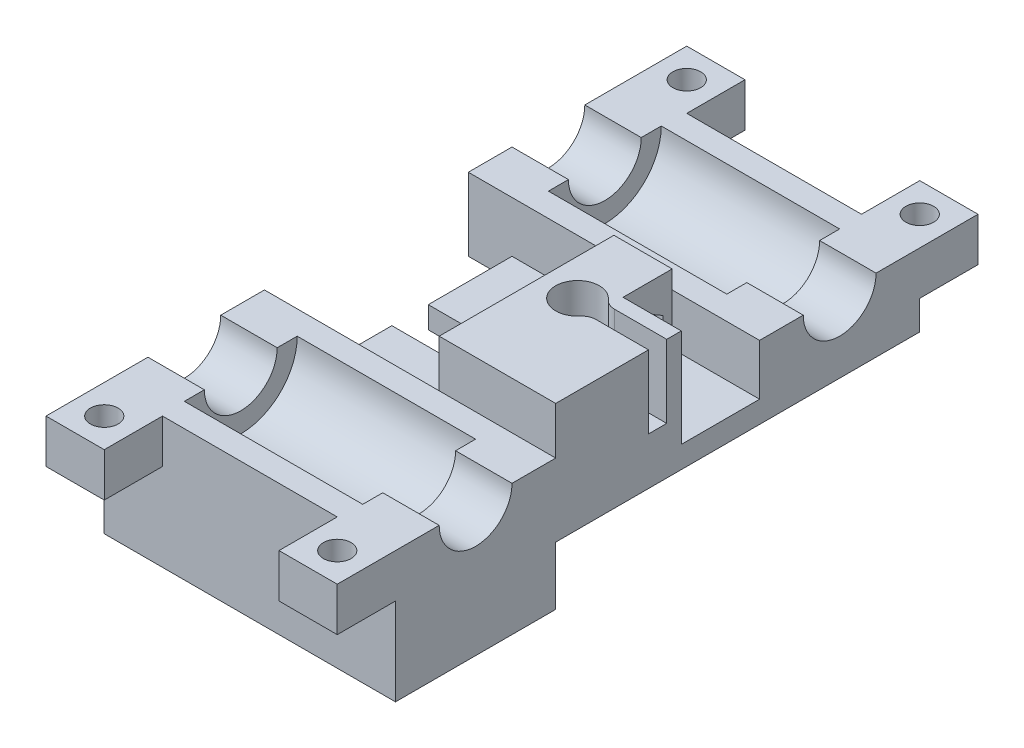
SolidWorks part; units mm, degrees
ref_plane "Front Plane" through (0, 0, 0) normal (0, 0, 1) x (1, 0, 0)
ref_plane "Top Plane" through (0, 0, 0) normal (0, 1, 0) x (1, 0, 0)
ref_plane "Right Plane" through (0, 0, 0) normal (1, 0, 0) x (0, 0, -1)
sketch "Sketch1" plane through (0, 0, 0) normal (0, 1, 0) x (1, 0, 0)
  line L1 (-20, 11) -> (20, 11)
  line L2 (-20, 11) -> (-20, -11)
  line L3 (-20, -11) -> (20, -11)
  line L4 (20, 11) -> (20, -11)
  line L5 (-20, 11) -> (20, -11) construction
  line L6 (-20, -11) -> (20, 11) construction
  point P0 (0, 0)
  dimension "D1" = 40
  dimension "D2" = 22
extrude "Boss-Extrude1" add sketch "Sketch1" along normal blind 11
sketch "Sketch2" plane through (0, 0, 0) normal (0, 1, 0) x (1, 0, 0)
  line L4 (20, -11) -> (20, 11)
  line L5 (-20, -11) -> (20, -11)
  line L6 (-20, 11) -> (-20, -11)
  line L7 (20, 11) -> (-20, 11)
  line L8 (20, -11) -> (20, 11)
  line L9 (-20, -11) -> (20, -11)
  line L10 (-20, 11) -> (-20, -11)
  line L11 (20, 11) -> (-20, 11)
  circle A0 centre (0, 0) radius 4.25
  dimension "D2" = 8.5
  dimension "D1" = 0
extrude "Boss-Extrude2" add sketch "Sketch2" against normal blind 7
sketch "Sketch3" plane through (0, 11, 0) normal (0, 1, 0) x (1, 0, 0)
  line L1 (12.25, -7.75) -> (-12.25, -7.75)
  line L2 (12.25, -7.75) -> (12.25, 7.75)
  line L3 (12.25, 7.75) -> (-12.25, 7.75)
  line L4 (-12.25, -7.75) -> (-12.25, 7.75)
  line L5 (12.25, -7.75) -> (-12.25, 7.75) construction
  line L6 (12.25, 7.75) -> (-12.25, -7.75) construction
  point P0 (0, 0)
  dimension "D1" = 15.5
  dimension "D2" = 24.5
extrude "Cut-Extrude1" cut sketch "Sketch3" against normal blind 7.75
fillet "Fillet1" radius 7.75 2 edges at (0, 3.25, 7.75) (0, 3.25, -7.75)
sketch "Sketch4" plane through (-12.25, 0, 0) normal (1, 0, 0) x (0, 0, -1)
  line L0 (7.75, 11) -> (-7.75, 11) construction
  circle A0 centre (0, 11) radius 5
  dimension "D1" = 10
extrude "Cut-Extrude2" cut sketch "Sketch4" against normal through all both and the other way through all
sketch "Sketch5" plane through (0, 11, 0) normal (0, 1, 0) x (1, 0, 0)
  line L1 (20, -11) -> (12, -11)
  line L2 (20, -11) -> (20, -19)
  line L3 (20, -19) -> (12, -19)
  line L4 (12, -11) -> (12, -19)
  circle A0 centre (16, -15) radius 1.9058
  dimension "D1" = 8
  dimension "D2" = 8
  dimension "D3" = 4
  dimension "D4" = 4
extrude "Boss-Extrude3" add sketch "Sketch5" against normal blind 6
sketch "Sketch6" plane through (0, 5, 0) normal (0, -1, 0) x (1, 0, 0)
  line L4 (20, 11) -> (20, 19)
  line L5 (20, 19) -> (12, 19)
  line L6 (12, 19) -> (12, 11)
  line L7 (12, 11) -> (20, 11)
  line L8 (20, 11) -> (20, 19)
  line L9 (20, 19) -> (12, 19)
  line L10 (12, 19) -> (12, 11)
  line L11 (12, 11) -> (20, 11)
  circle A0 centre (16, 15) radius 1.9058 construction
  circle A1 centre (16, 15) radius 1.9058
  circle A2 centre (16, 15) radius 3
  circle M6 centre (16, 15) radius 1.9058
  dimension "D2" = 6
  dimension "D1" = 0
extrude "Cut-Extrude3" cut sketch "Sketch6" against normal blind 3 contours A2 M6 region at (13.0849, 5, 15)
mirror "Mirror8" about plane through (0, 0, 0) normal (1, 0, 0) of "Cut-Extrude3", "Boss-Extrude3"
mirror "Mirror9" [suppressed] about plane through (0, 0, 0) normal (0, 0, 1)
chamfer "Chamfer2" [suppressed] distance 4 angle 45
ref_plane "Plane1" through (0, 0, -25) normal (0, 0, 1) x (1, 0, 0)
sketch "Sketch7" plane through (0, 0, -11) normal (0, 0, -1) x (-1, 0, 0)
  line L0 (-20, 11) -> (-20, -7) construction
  line L1 (-20, 1) -> (-4, 1)
  line L2 (-20, 1) -> (-20, 17.5)
  line L3 (-20, 17.5) -> (-4, 17.5)
  line L4 (-4, 1) -> (-4, 17.5)
  line L5 (-20, 11) -> (20, 11) construction
  dimension "D1" = 16
  dimension "D2" = 16.5
  dimension "D3" = 6.5
extrude "Boss-Extrude5" add sketch "Sketch7" along normal blind 28
mirror "Mirror14" about plane through (0, 0, -25) normal (0, 0, 1) of "Mirror8", "Cut-Extrude3", "Boss-Extrude3", "Cut-Extrude2", "Fillet1", "Cut-Extrude1", "Boss-Extrude2", "Boss-Extrude1"
sketch "Sketch9" plane through (4, 0, 0) normal (-1, 0, 0) x (0, 0, 1)
  line L0 (-39, 1) -> (-39, 11) construction
  line L1 (-11, 1) -> (-39, 1)
  line L2 (-11, 1) -> (-11, 4)
  line L3 (-11, 4) -> (-39, 4)
  line L4 (-39, 1) -> (-39, 4)
  dimension "D1" = 3
extrude "Boss-Extrude6" add sketch "Sketch9" along normal blind 18
sketch "Sketch10" plane through (0, 17.5, 0) normal (0, 1, 0) x (1, 0, 0)
  line L0 (-13.475, 25) -> (13.475, 25) construction
  line L1 (20, 39) -> (20, 11) construction
  line L3 (9, 23.75) -> (20, 23.75)
  line L4 (9, 23.75) -> (9, 26.25)
  line L5 (9, 26.25) -> (20, 26.25)
  line L6 (20, 23.75) -> (20, 26.25)
  circle A0 centre (9, 25) radius 3
  line M4 (20, 11) -> (20, 39)
  dimension "D3" = 6
  dimension "D1" = 0
  dimension "D2" = 11
  dimension "D4" = 2.5
  dimension "D5" = 1.25
extrude "Cut-Extrude4" cut sketch "Sketch10" against normal blind 10 contours L3 A0 L5 L4 | L5 A0 L3 L4 | A0 L3 L5 M4 region at (10.4565, 17.5, -25) region at (8.4952, 17.5, -25) region at (15.955, 17.5, -25)
sketch "Sketch11" plane through (0, 7.5, 0) normal (0, 1, 0) x (1, 0, 0)
  arc A0 (11.7272, 26.25) -> (11.7272, 23.75) centre (9, 25) ccw construction
  arc A1 (11.7272, 26.25) -> (11.7272, 23.75) centre (9, 25) ccw
  circle A2 centre (9, 25) radius 1.75
  dimension "D1" = 3.5
extrude "Cut-Extrude5" cut sketch "Sketch11" against normal through all both and the other way through all contours A2 region at (9, 7.5, -25)
sketch "Sketch12" plane through (4, 0, 0) normal (-1, 0, 0) x (0, 0, 1)
  line L1 (-39, 4) -> (-39, 11) construction
  circle A0 centre (-31, 11) radius 1.75
  dimension "D3" = 3.5
  dimension "D1" = 0
  dimension "D2" = 8
extrude "Cut-Extrude6" cut sketch "Sketch12" against normal through all both and the other way through all
sketch "Sketch15" plane through (20, 0, 0) normal (1, 0, 0) x (0, 0, -1)
  line L1 (32.6923, 13.6869) -> (29.5192, 13.809)
  line L2 (29.5192, 13.809) -> (27.8269, 11.1221)
  line L3 (27.8269, 11.1221) -> (29.3077, 8.3131)
  line L4 (29.3077, 8.3131) -> (32.4808, 8.191)
  line L5 (32.4808, 8.191) -> (34.1731, 10.8779)
  line L6 (34.1731, 10.8779) -> (32.6923, 13.6869)
  circle A0 centre (31, 11) radius 1.75 construction
  circle A1 centre (31, 11) radius 1.75
  circle A2 centre (31, 11) radius 2.75 construction
  dimension "D1" = 5.5
extrude "Cut-Extrude9" [suppressed] cut sketch "Sketch15" against normal blind 12 contours L1 L2 L3 L4 L5 L6
sketch "Sketch16" [suppressed] plane through (20, 0, 0) normal (1, 0, 0) x (0, 0, -1)
  line L1 (27, 11) -> (39, 11)
  line L2 (27, 11) -> (27, 17.5)
  line L3 (27, 17.5) -> (39, 17.5)
  line L4 (39, 11) -> (39, 17.5)
  circle A0 centre (31, 11) radius 1.75 construction
  circle A1 centre (31, 11) radius 1.75
  circle A2 centre (31, 11) radius 4
  dimension "D1" = 8
extrude "Cut-Extrude11" [suppressed] cut sketch "Sketch16" against normal blind 8
chamfer "Chamfer3" [suppressed] distance 2.5 angle 45
fillet "Fillet2" radius 2 2 edges at (11.7272, 12.5, -23.75) (11.7272, 12.5, -26.25)
sketch "Sketch17" plane through (0, 1, 0) normal (0, -1, 0) x (1, 0, 0)
  line L1 (12.1754, -25) -> (10.5877, -22.25)
  line L2 (10.5877, -22.25) -> (7.4123, -22.25)
  line L3 (7.4123, -22.25) -> (5.8246, -25)
  line L4 (5.8246, -25) -> (7.4123, -27.75)
  line L5 (7.4123, -27.75) -> (10.5877, -27.75)
  line L6 (10.5877, -27.75) -> (12.1754, -25)
  circle A0 centre (9, -25) radius 1.75 construction
  circle A1 centre (9, -25) radius 1.75
  circle A2 centre (9, -25) radius 2.75 construction
  dimension "D1" = 5.5
extrude "Cut-Extrude12" cut sketch "Sketch17" against normal blind 3
sketch "Sketch18" plane through (0, 4, 0) normal (0, 1, 0) x (1, 0, 0)
  line L0 (-14, 11) -> (-14, 39) construction
  line L1 (-14, 22.5) -> (4, 22.5)
  line L2 (-14, 22.5) -> (-14, 27.5)
  line L3 (-14, 27.5) -> (4, 27.5)
  line L4 (4, 22.5) -> (4, 27.5)
  line L5 (-13.475, 25) -> (13.475, 25) construction
  dimension "D1" = 2.5
  dimension "D2" = 5
  dimension "D3" = 18
extrude "Cut-Extrude13" cut sketch "Sketch18" against normal through all both and the other way through all
fillet "Fillet3" radius 2.5 2 edges at (4, 2.5, -27.5) (4, 2.5, -22.5)
sketch "Sketch19" plane through (0, 1, 0) normal (0, -1, 0) x (1, 0, 0)
  line L4 (20, -39) -> (-20, -39)
  line L5 (-20, -39) -> (-20, -61)
  line L6 (-20, -61) -> (20, -61)
  line L7 (-14, -22.5) -> (1.5, -22.5)
  line L8 (1.5, -27.5) -> (-14, -27.5)
  line L9 (-14, -27.5) -> (-14, -39)
  line L10 (-14, -39) -> (20, -39)
  line L11 (20, -39) -> (20, -11)
  line L12 (20, -11) -> (-14, -11)
  line L13 (-14, -11) -> (-14, -22.5)
  line L14 (-14, -22.5) -> (1.5, -22.5)
  line L15 (1.5, -27.5) -> (-14, -27.5)
  line L16 (-14, -27.5) -> (-14, -39)
  line L17 (-14, -39) -> (20, -39)
  line L18 (20, -39) -> (20, -11)
  line L19 (20, -11) -> (-14, -11)
  line L20 (-14, -11) -> (-14, -22.5)
  line L21 (20, -61) -> (20, -39)
  line L22 (20, -39) -> (-20, -39)
  line L23 (-20, -39) -> (-20, -61)
  line L24 (-20, -61) -> (20, -61)
  line L25 (20, -61) -> (20, -39)
  arc A2 (4, -25) -> (1.5, -22.5) centre (1.5, -25) ccw
  arc A3 (1.5, -27.5) -> (4, -25) centre (1.5, -25) ccw
  arc A4 (4, -25) -> (1.5, -22.5) centre (1.5, -25) ccw
  arc A5 (1.5, -27.5) -> (4, -25) centre (1.5, -25) ccw
  line M25 (-14, -39) -> (20, -39)
  dimension "D1" = 0
  dimension "D2" = 0
extrude "Cut-Extrude14" cut sketch "Sketch19" along normal through all contours L24 L25 L22 L23 M25 region at (0, 1, -50)
sketch "Sketch20" plane through (0, 17.5, 0) normal (0, 1, 0) x (1, 0, 0)
  line L1 (4, 39) -> (40.1637, 39)
  line L2 (4, 39) -> (4, 35)
  line L3 (4, 35) -> (40.1637, 35)
  line L4 (40.1637, 39) -> (40.1637, 35)
  dimension "D1" = 4
sketch "Sketch21" plane through (20, 0, 0) normal (1, 0, 0) x (0, 0, -1)
  line L1 (31, 14.1754) -> (28.25, 12.5877)
  line L2 (28.25, 12.5877) -> (28.25, 9.4123)
  line L3 (28.25, 9.4123) -> (31, 7.8246)
  line L4 (31, 7.8246) -> (33.75, 9.4123)
  line L5 (33.75, 9.4123) -> (33.75, 12.5877)
  line L6 (33.75, 12.5877) -> (31, 14.1754)
  circle A0 centre (31, 11) radius 1.75 construction
  circle A1 centre (31, 11) radius 1.75
  circle A2 centre (31, 11) radius 2.75 construction
  dimension "D1" = 5.5
extrude "Cut-Extrude15" cut sketch "Sketch21" against normal blind 10
extrude "Cut-Extrude16" cut sketch "Sketch20" against normal up to surface (13.5 mm away) up to face at (-3.5964, 4, -31.7036)
sketch "Sketch22" plane through (20, 0, 0) normal (1, 0, 0) x (0, 0, -1)
  line L0 (28.25, 12.5877) -> (28.25, 9.4123) construction
  line L1 (35, 17.5) -> (28.25, 17.5)
  line L2 (35, 17.5) -> (35, 4)
  line L3 (35, 4) -> (28.25, 4)
  line L4 (28.25, 17.5) -> (28.25, 4)
  line L5 (39, 4) -> (35, 4) construction
  dimension "D1" = 0
  dimension "D2" = 0
extrude "Cut-Extrude18" cut sketch "Sketch22" against normal blind 8
sketch "Sketch23" plane through (0, 0, 0) normal (0, -1, 0) x (1, 0, 0)
  circle A1 centre (0, 0) radius 4.25
  circle A2 centre (0, 0) radius 4.25
  dimension "D1" = 0
extrude "Boss-Extrude8" add sketch "Sketch23" along normal blind 1
